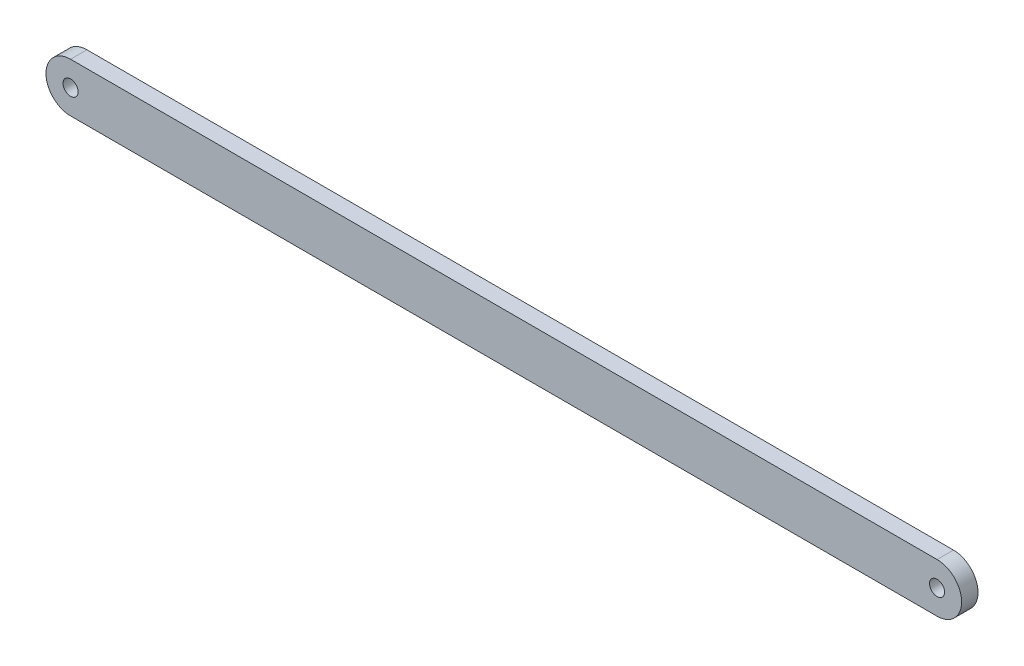
SolidWorks part; units mm, degrees
ref_plane "前视基准面" through (0, 0, 0) normal (0, 0, 1) x (1, 0, 0)
ref_plane "上视基准面" through (0, 0, 0) normal (0, 1, 0) x (1, 0, 0)
ref_plane "右视基准面" through (0, 0, 0) normal (1, 0, 0) x (0, 0, -1)
other "Configuration Table"
sketch "草图1" plane through (0, 0, 0) normal (0, 0, 1) x (1, 0, 0)
  line L1 (-132.3, 7.5) -> (132.3, 7.5)
  line L3 (-132.3, -7.5) -> (132.3, -7.5)
  line L5 (-132.3, 7.5) -> (132.3, -7.5) construction
  line L6 (-132.3, -7.5) -> (132.3, 7.5) construction
  arc A0 (-132.3, 7.5) -> (-132.3, -7.5) centre (-132.3, 0) ccw
  arc A1 (132.3, 7.5) -> (132.3, -7.5) centre (132.3, 0) cw
  circle A2 centre (-132.3, 0) radius 2.3
  circle A3 centre (132.3, 0) radius 2.3
  point P0 (0, 0)
  dimension "D1" = 4.6
  dimension "D2" = 4.6
  dimension "D3" = 264.6
  dimension "D4" = 15
extrude "凸台-拉伸1" add sketch "草图1" along normal blind 5
equation "\"fi\"=4.6"
equation "\"D1@草图1\"=\"fi\""
equation "\"D2@草图1\"=\"fi\""
equation "\"b0\"=75.6"
equation "\"D3@草图1\"=\"b4\""
equation "\"width\"=15"
equation "\"D4@草图1\"=\"width\""
equation "\"depth\"=5"
equation "\"D1@凸台-拉伸1\"=\"depth\""
equation "\"b1\"= \"b0\" * 3 / 2"
equation "\"b2\"= \"b0\" * 6 / 2"
equation "\"b3\"= \"b0\" * 4 / 2"
equation "\"b4\"= \"b0\" * 7 / 2"
equation "\"angle\"= 90度"
